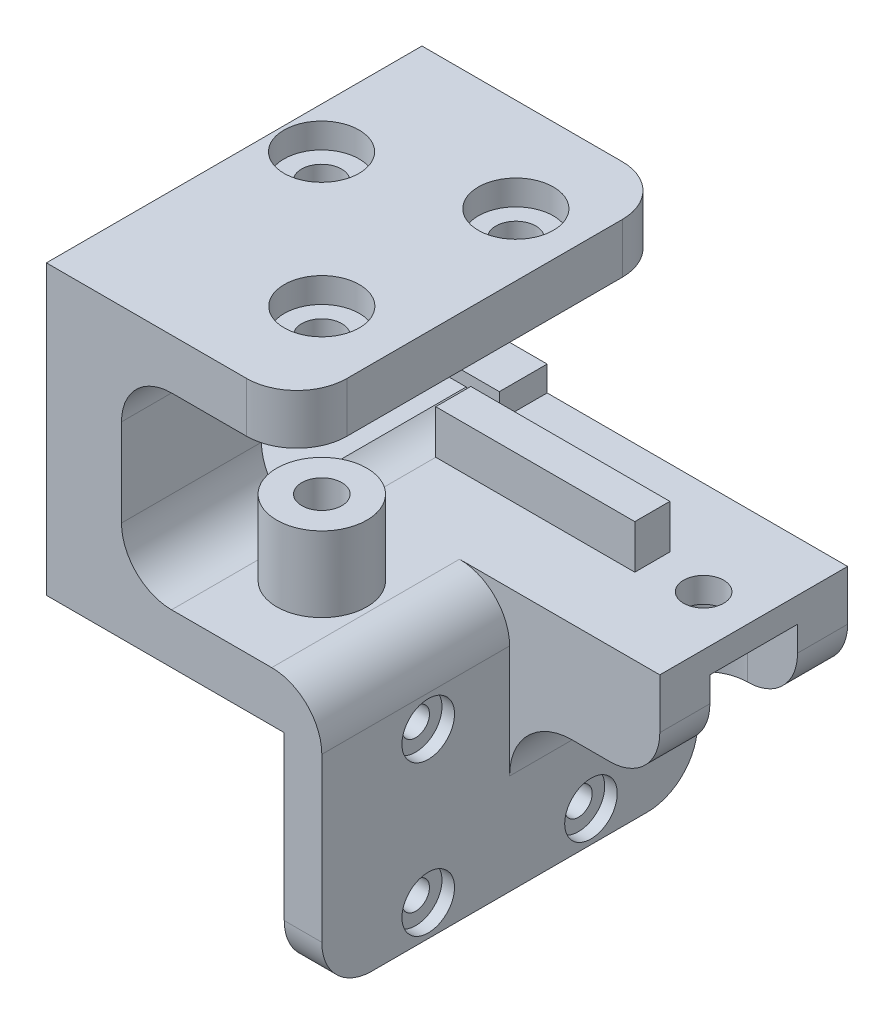
SolidWorks part; units mm, degrees
ref_plane "Plano frontal" through (0, 0, 0) normal (0, 0, 1) x (1, 0, 0)
ref_plane "Plano superior" through (0, 0, 0) normal (0, 1, 0) x (1, 0, 0)
ref_plane "Plano direito" through (0, 0, 0) normal (1, 0, 0) x (0, 0, -1)
sketch "Esboço1" plane through (0, 0, 0) normal (0, 0, 1) x (1, 0, 0)
  line L0 (0, 0) -> (3, 0)
  line L3 (15, 21) -> (-13, 21)
  line L4 (-13, 21) -> (-13, 36)
  line L5 (-13, 36) -> (1, 36)
  line L6 (1, 36) -> (1, 40)
  line L7 (1, 40) -> (-19, 40)
  line L9 (-19, 17) -> (0, 17)
  line L10 (0, 17) -> (0, 0)
  line L12 (15, 21) -> (15, 13)
  line L13 (3, 0) -> (3, 8)
  line L14 (15, 13) -> (31.662, 13) construction
  line L16 (-19, 17) -> (-19, 40)
  line L19 (8, 13) -> (15, 13)
  arc A0 (3, 8) -> (8, 13) centre (8, 8) cw
  dimension "D10" = 5
  dimension "D1" = 3
  dimension "D2" = 17
  dimension "D3" = 15
  dimension "D4" = 4
  dimension "D5" = 6
  dimension "D6" = 19
  dimension "D7" = 1
  dimension "D8" = 8
  dimension "D9" = 4
  dimension "D12" = 15
extrude "Ressalto-extrusão1" add sketch "Esboço1" along normal blind 30
sketch "Esboço3" plane through (0, 0, 0) normal (1, 0, 0) x (0, 0, -1)
  line L0 (0, 8.5) -> (-30, 8.5) construction
  line L1 (0, 17) -> (0, 0) construction
  line L2 (-30, 17) -> (-30, 0) construction
  line L4 (-30, 0) -> (0, 0) construction
  line L5 (-15, 0) -> (-15, 15) construction
  circle A0 centre (-8.5, 14.5) radius 1.1
  circle A4 centre (-21.5, 14.5) radius 1.1
  circle A5 centre (-8.5, 2.5) radius 1.1
  circle A6 centre (-21.5, 2.5) radius 1.1
  dimension "D3" = 2.2
  dimension "D1" = 12
  dimension "D2" = 13
extrude "Corte-extrusão1" cut sketch "Esboço3" against normal through all both and the other way through all
sketch "Esboço4" plane through (0, 0, 0) normal (0, 1, 0) x (1, 0, 0)
  line L0 (15, -15) -> (3, -15)
  line L1 (15, -30) -> (15, 0) construction
  line L2 (3, -30) -> (3, 0) construction
  line L3 (3, -15) -> (3, -30)
  line L4 (15, -15) -> (15, -30)
  line L5 (15, -30) -> (3, -30)
  line L6 (15, 0) -> (-13, 0) construction
  dimension "D1" = 15
extrude "Corte-extrusão6" cut sketch "Esboço4" against normal through all and the other way through all
sketch "Esboço5" plane through (0, 40, 0) normal (0, 1, 0) x (1, 0, 0)
  line L0 (1, -30) -> (-19, -30) construction
  line L1 (15, -15) -> (15, 0) construction
  line L2 (15, -15) -> (15, 0) construction
  circle A0 centre (-5, -22) radius 1.6
  circle A1 centre (-15.7, -11.32) radius 1.6
  circle A2 centre (-5, -22) radius 4.84 construction
  circle A3 centre (-15.7, -11.32) radius 4.84 construction
  circle A4 centre (11, -7.5) radius 1.6
  point P15 (15, -7.5)
  dimension "D2" = 3.2
  dimension "D5" = 9.68
  dimension "D6" = 1
  dimension "D1" = 8
  dimension "D3" = 5
  dimension "D4" = 15.7
  dimension "D7" = 4
extrude "Corte-extrusão7" cut sketch "Esboço5" against normal through all
sketch "Esboço7" plane through (0, 21, 0) normal (0, 1, 0) x (1, 0, 0)
  line L1 (-23.2, -3.82) -> (-8.2, -3.82)
  line L2 (-23.2, -3.82) -> (-23.2, -18.82)
  line L3 (-23.2, -18.82) -> (-8.2, -18.82)
  line L4 (-8.2, -3.82) -> (-8.2, -18.82)
  circle A0 centre (-15.7, -11.32) radius 7.5 construction
  dimension "D1" = 15
extrude "Corte-extrusão9" cut sketch "Esboço7" along normal offset from surface (8 mm away) 6 from offset 1 up to face at (-5, 36, 23.6)
sketch "Esboço9" plane through (0, 40, 0) normal (0, 1, 0) x (1, 0, 0)
  line L0 (1, -30) -> (1, 0) construction
  circle A1 centre (-4, -7.5) radius 1.6
  point P0 (11, -7.5)
  point P6 (11, -7.5)
  dimension "D1" = 3.2
  dimension "D3" = 5
extrude "Corte-extrusão11" cut sketch "Esboço9" against normal up to next
sketch "Esboço8" plane through (0, 40, 0) normal (0, 1, 0) x (1, 0, 0)
  circle A0 centre (-15.7, -11.32) radius 3
  circle A1 centre (-5, -22) radius 3
  circle A3 centre (-4, -7.5) radius 3
  circle A4 centre (-4, -7.5) radius 1.6 construction
  point P8 (-4, -15)
  dimension "D1" = 6
extrude "Corte-extrusão10" cut sketch "Esboço8" against normal blind 2
sketch "Esboço14" plane through (0, 17, 0) normal (0, -1, 0) x (1, 0, 0)
  line L0 (11, 11) -> (15, 11)
  line L1 (-5, 25.2332) -> (-7.8, 23.6166)
  line L2 (-7.8, 23.6166) -> (-7.8, 20.3834)
  line L3 (-7.8, 20.3834) -> (-5, 18.7668)
  line L4 (-5, 18.7668) -> (-2.2, 20.3834)
  line L5 (-2.2, 20.3834) -> (-2.2, 23.6166)
  line L6 (-2.2, 23.6166) -> (-5, 25.2332)
  line L7 (-15.7, 14.5532) -> (-18.5, 12.9366)
  line L8 (-18.5, 12.9366) -> (-18.5, 9.7034)
  line L9 (-18.5, 9.7034) -> (-15.7, 8.0868)
  line L10 (-15.7, 8.0868) -> (-12.9, 9.7034)
  line L11 (-12.9, 9.7034) -> (-12.9, 12.9366)
  line L12 (-12.9, 12.9366) -> (-15.7, 14.5532)
  line L13 (15, 11) -> (15, 4)
  line L14 (15, 15) -> (15, 0) construction
  line L15 (15, 4) -> (11, 4)
  circle A0 centre (-5, 22) radius 2.8 construction
  circle A1 centre (-15.7, 11.32) radius 2.8 construction
  arc A2 (11, 11) -> (11, 4) centre (11, 7.5) ccw
  dimension "D1" = 5.6
  dimension "D2" = 7
extrude "Corte-extrusão14" cut sketch "Esboço14" against normal blind 2 and the other way through all
sketch "Esboço15" plane through (3, 0, 0) normal (1, 0, 0) x (0, 0, -1)
  circle A0 centre (-21.5, 14.5) radius 2.1
  circle A1 centre (-8.5, 14.5) radius 2.1
  circle A2 centre (-8.5, 2.5) radius 2.1
  circle A3 centre (-21.5, 2.5) radius 2.1
  dimension "D1" = 4.2
extrude "Corte-extrusão16" cut sketch "Esboço15" against normal offset from surface 2 and the other way through all up to face at (0, 15.6, 21.5)
fillet "Filete1" radius 4 9 edges at (1.5, 0, 0) (1.5, 0, 30) (3, 21, 22.5) (1, 38, 0) (-13, 21, 15) (15, 13, 2) (15, 13, 13) (1, 38, 30) (-13, 36, 15)
sketch "Esboço16" plane through (0, 21, 0) normal (0, 1, 0) x (1, 0, 0)
  line L0 (15, 0) -> (-9, 0) construction
  line L1 (-19, -3.82) -> (-9, -3.82)
  line L2 (-19, -3.82) -> (-19, 0)
  line L3 (-19, 0) -> (-9, 0)
  line L4 (-9, -3.82) -> (-9, 0)
  line L5 (-19, -30) -> (-19, 0) construction
  line L6 (15, 0) -> (-9, 0) construction
  line L7 (-11.6458, -3.82) -> (-19, -3.82) construction
  point P7 (0, 0)
  point P8 (-20.2921, -6.5984)
  point P11 (-5.5716, 0)
  point P15 (0, 0)
  dimension "D1" = 4
extrude "Ressalto-extrusão2" add sketch "Esboço16" along normal blind 2
sketch "Esboço17" plane through (0, 21, 0) normal (0, 1, 0) x (1, 0, 0)
  line L0 (-9, -3.82) -> (-9, 0) construction
  line L1 (-9, -6.1) -> (6.9, -6.1)
  line L2 (-9, -6.1) -> (-9, -8.9)
  line L3 (-9, -8.9) -> (6.9, -8.9)
  line L4 (6.9, -6.1) -> (6.9, -8.9)
  line L5 (-9, -6.1) -> (6.9, -8.9) construction
  line L6 (-9, -8.9) -> (6.9, -6.1) construction
  circle A0 centre (11, -7.5) radius 1.6 construction
  point P0 (-1.05, -7.5)
  point P5 (11, -7.5)
  point P6 (0, 0)
  dimension "D1" = 2.5
  dimension "D2" = 2.8
extrude "Ressalto-extrusão3" add sketch "Esboço17" along normal blind 3.5
sketch "Esboço20" plane through (0, 21, 0) normal (0, 1, 0) x (1, 0, 0)
  circle A0 centre (-5, -22) radius 3.6
  circle A1 centre (-5, -22) radius 1.6
  circle A2 centre (-5, -22) radius 1.6 construction
  dimension "D1" = 2
extrude "Ressalto-extrusão4" add sketch "Esboço20" against normal blind 1 and the other way blind 6
